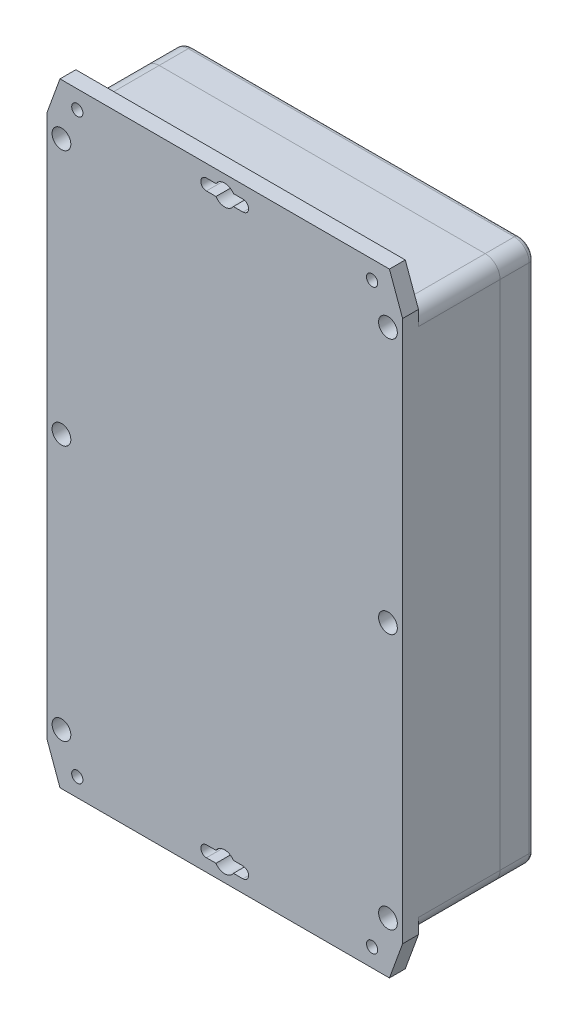
SolidWorks part; units mm, degrees
ref_plane "Front Plane" through (0, 0, 0) normal (0, 0, 1) x (1, 0, 0)
ref_plane "Top Plane" through (0, 0, 0) normal (0, 1, 0) x (1, 0, 0)
ref_plane "Right Plane" through (0, 0, 0) normal (1, 0, 0) x (0, 0, -1)
sketch "Sketch1" plane through (0, 0, 0) normal (0, 0, 1) x (1, 0, 0)
  line L0 (-73.025, -125.9967) -> (73.025, 125.9967) construction
  line L1 (-73.025, 125.9967) -> (73.025, 125.9967)
  line L2 (-73.025, 125.9967) -> (-73.025, -125.9967)
  line L3 (-73.025, -125.9967) -> (73.025, -125.9967)
  line L4 (73.025, 125.9967) -> (73.025, -125.9967)
  line L5 (0, 118.5037) -> (0, -118.5037) construction
  line L6 (-7.5057, 118.5037) -> (7.5057, 118.5037) construction
  line L7 (-7.5057, 120.8024) -> (-3.58, 120.8024)
  line L8 (-7.5057, 116.205) -> (-3.58, 116.205)
  line L9 (3.58, 120.8024) -> (7.5057, 120.8024)
  line L10 (3.58, 116.205) -> (7.5057, 116.205)
  line L11 (-73.025, 0) -> (73.025, 0) construction
  line L12 (-7.5057, -116.205) -> (-3.58, -116.205)
  line L13 (3.58, -116.205) -> (7.5057, -116.205)
  line L14 (3.58, -120.8024) -> (7.5057, -120.8024)
  line L15 (-7.5057, -120.8024) -> (-3.58, -120.8024)
  line L16 (-67.0052, 105.0036) -> (67.0052, -105.0036) construction
  line L17 (0, -114.2492) -> (0, -122.7582) construction
  line L18 (0, 114.2492) -> (0, 122.7582) construction
  line L19 (-60.5028, 118.5037) -> (60.5028, 118.5037) construction
  line L20 (-60.5028, -118.5037) -> (60.5028, -118.5037) construction
  line L21 (0, -118.5037) -> (0, 118.5037) construction
  arc A0 (3.58, 120.8024) -> (-3.58, 120.8024) centre (0, 118.5037) ccw
  arc A1 (-7.5057, 120.8024) -> (-7.5057, 116.205) centre (-7.5057, 118.5037) ccw
  arc A2 (7.5057, 116.205) -> (7.5057, 120.8024) centre (7.5057, 118.5037) ccw
  arc A3 (-3.58, 116.205) -> (3.58, 116.205) centre (0, 118.5037) ccw
  arc A4 (-3.58, -116.205) -> (3.58, -116.205) centre (0, -118.5037) cw
  arc A5 (7.5057, -116.205) -> (7.5057, -120.8024) centre (7.5057, -118.5037) cw
  arc A6 (3.58, -120.8024) -> (-3.58, -120.8024) centre (0, -118.5037) cw
  arc A7 (-7.5057, -120.8024) -> (-7.5057, -116.205) centre (-7.5057, -118.5037) cw
  circle A8 centre (67.0052, 105.0036) radius 2.2225
  circle A9 centre (67.0052, 105.0036) radius 3.8481
  circle A10 centre (67.0052, -105.0036) radius 3.8481
  circle A11 centre (67.0052, -105.0036) radius 2.2225
  circle A12 centre (-67.0052, -105.0036) radius 3.8481
  circle A13 centre (-67.0052, -105.0036) radius 2.2225
  circle A14 centre (-67.0052, 105.0036) radius 3.8481
  circle A15 centre (-67.0052, 105.0036) radius 2.2225
  circle A16 centre (60.5028, 118.5037) radius 2.2987
  circle A17 centre (-60.5028, 118.5037) radius 2.2987
  circle A18 centre (-60.5028, -118.5037) radius 2.2987
  circle A19 centre (60.5028, -118.5037) radius 2.2987
  circle A20 centre (-67.0052, 0) radius 3.8481
  circle A21 centre (-67.0052, 0) radius 2.2225
  circle A22 centre (67.0052, 0) radius 3.8481
  circle A23 centre (67.0052, 0) radius 2.2225
  dimension "D4" = 8.509
  dimension "D5" = 4.5974
  dimension "D7" = 7.6962
  dimension "D8" = 4.445
  dimension "Width" = 146.05
  dimension "Total Height" = 251.9934
  dimension "Hole Location" = 237.0074
  dimension "D6" = 15.0114
  dimension "A" = 210.0072
  dimension "B" = 134.0104
  dimension "flange holes" = 121.0056
sketch "Sketch18" plane through (0, 0, 0) normal (1, 0, 0) x (0, 0, -1)
  line L0 (0, 0) -> (53.975, 0) construction
  point P3 (40.005, 0)
  dimension "Depth" = 53.975
  dimension "Base Depth" = 40.005
sketch "Sketch2" plane through (0, 0, 0) normal (0, 0, 1) x (1, 0, 0)
  line L4 (73.025, 125.9967) -> (-73.025, 125.9967)
  line L5 (73.025, -125.9967) -> (73.025, 125.9967)
  line L6 (-73.025, -125.9967) -> (73.025, -125.9967)
  line L7 (-73.025, 125.9967) -> (-73.025, -125.9967)
  line L8 (73.025, 125.9967) -> (-73.025, 125.9967)
  line L9 (73.025, -125.9967) -> (73.025, 125.9967)
  line L10 (-73.025, -125.9967) -> (73.025, -125.9967)
  line L11 (-73.025, 125.9967) -> (-73.025, -125.9967)
  line L12 (-7.5057, -120.8024) -> (-3.58, -120.8024)
  line L13 (3.58, -120.8024) -> (7.5057, -120.8024)
  line L14 (7.5057, -116.205) -> (3.58, -116.205)
  line L15 (-3.58, -116.205) -> (-7.5057, -116.205)
  line L16 (-7.5057, -120.8024) -> (-3.58, -120.8024)
  line L17 (3.58, -120.8024) -> (7.5057, -120.8024)
  line L18 (7.5057, -116.205) -> (3.58, -116.205)
  line L19 (-3.58, -116.205) -> (-7.5057, -116.205)
  line L20 (-3.58, 120.8024) -> (-7.5057, 120.8024)
  line L21 (-7.5057, 116.205) -> (-3.58, 116.205)
  line L22 (3.58, 116.205) -> (7.5057, 116.205)
  line L23 (7.5057, 120.8024) -> (3.58, 120.8024)
  line L24 (-3.58, 120.8024) -> (-7.5057, 120.8024)
  line L25 (-7.5057, 116.205) -> (-3.58, 116.205)
  line L26 (3.58, 116.205) -> (7.5057, 116.205)
  line L27 (7.5057, 120.8024) -> (3.58, 120.8024)
  circle A0 centre (60.5028, 118.5037) radius 2.2987 construction
  circle A1 centre (-60.5028, 118.5037) radius 2.2987 construction
  circle A2 centre (-60.5028, -118.5037) radius 2.2987 construction
  circle A3 centre (60.5028, -118.5037) radius 2.2987 construction
  circle A4 centre (60.5028, 118.5037) radius 2.2987
  circle A5 centre (-60.5028, 118.5037) radius 2.2987
  circle A6 centre (-60.5028, -118.5037) radius 2.2987
  circle A7 centre (60.5028, -118.5037) radius 2.2987
  arc A8 (-7.5057, -116.205) -> (-7.5057, -120.8024) centre (-7.5057, -118.5037) ccw
  arc A9 (-3.58, -120.8024) -> (3.58, -120.8024) centre (0, -118.5037) ccw
  arc A10 (7.5057, -120.8024) -> (7.5057, -116.205) centre (7.5057, -118.5037) ccw
  arc A11 (3.58, -116.205) -> (-3.58, -116.205) centre (0, -118.5037) ccw
  arc A12 (-7.5057, -116.205) -> (-7.5057, -120.8024) centre (-7.5057, -118.5037) ccw
  arc A13 (-3.58, -120.8024) -> (3.58, -120.8024) centre (0, -118.5037) ccw
  arc A14 (7.5057, -120.8024) -> (7.5057, -116.205) centre (7.5057, -118.5037) ccw
  arc A15 (3.58, -116.205) -> (-3.58, -116.205) centre (0, -118.5037) ccw
  arc A16 (-7.5057, 120.8024) -> (-7.5057, 116.205) centre (-7.5057, 118.5037) ccw
  arc A17 (-3.58, 116.205) -> (3.58, 116.205) centre (0, 118.5037) ccw
  arc A18 (7.5057, 116.205) -> (7.5057, 120.8024) centre (7.5057, 118.5037) ccw
  arc A19 (3.58, 120.8024) -> (-3.58, 120.8024) centre (0, 118.5037) ccw
  arc A20 (-7.5057, 120.8024) -> (-7.5057, 116.205) centre (-7.5057, 118.5037) ccw
  arc A21 (-3.58, 116.205) -> (3.58, 116.205) centre (0, 118.5037) ccw
  arc A22 (7.5057, 116.205) -> (7.5057, 120.8024) centre (7.5057, 118.5037) ccw
  arc A23 (3.58, 120.8024) -> (-3.58, 120.8024) centre (0, 118.5037) ccw
  dimension "D1" = 0
  dimension "D4" = 0
  dimension "D5" = 0
extrude "Boss-Extrude1" add sketch "Sketch2" against normal blind 6.5024
sketch "Sketch3" plane through (0, 0, -6.5024) normal (0, 0, -1) x (-1, 0, 0)
  line L0 (73.025, 111.125) -> (67.6121, 125.9967)
  line L1 (-73.025, 111.125) -> (-67.6121, 125.9967)
  line L2 (73.025, -111.125) -> (67.6121, -125.9967)
  line L3 (-73.025, -111.125) -> (-67.6121, -125.9967)
  line L4 (73.025, -125.9967) -> (73.025, 125.9967)
  line L5 (73.025, 125.9967) -> (-73.025, 125.9967)
  line L6 (-73.025, 125.9967) -> (-73.025, -125.9967)
  line L7 (-73.025, -125.9967) -> (73.025, -125.9967)
  line L8 (73.025, -125.9967) -> (73.025, -111.125)
  line L9 (73.025, 125.9967) -> (67.6121, 125.9967)
  line L10 (-73.025, 125.9967) -> (-73.025, 111.125)
  line L11 (-73.025, -125.9967) -> (-67.6121, -125.9967)
  line L12 (-67.6121, 125.9967) -> (-73.025, 125.9967)
  line L13 (73.025, -125.9967) -> (-73.025, -125.9967) construction
  line L14 (67.6121, -125.9967) -> (73.025, -125.9967)
  line L15 (-73.025, -111.125) -> (-73.025, -125.9967)
  line L16 (73.025, 111.125) -> (73.025, 125.9967)
  line L19 (73.025, 111.125) -> (73.025, -111.125) construction
  dimension "D2" = 20
  dimension "D3" = 20
  dimension "Height" = 222.25
  dimension "D1" = 0
extrude "Cut-Extrude1" cut sketch "Sketch3" against normal through all
sketch "Sketch4" plane through (0, 0, -6.5024) normal (0, 0, 1) x (1, 0, 0)
  line L0 (-68.453, 106.553) -> (68.453, 106.553) construction
  line L1 (-73.025, 111.125) -> (73.025, 111.125)
  line L2 (-73.025, 111.125) -> (-73.025, -111.125)
  line L3 (-73.025, -111.125) -> (73.025, -111.125)
  line L4 (73.025, 111.125) -> (73.025, -111.125)
  line L5 (68.453, 106.553) -> (68.453, -106.553) construction
  line L6 (-68.453, -106.553) -> (68.453, -106.553) construction
  line L7 (-68.453, 106.553) -> (-68.453, -106.553) construction
  line L8 (-70.485, 108.585) -> (70.485, 108.585) construction
  line L9 (73.025, 125.9967) -> (73.025, -125.9967) construction
  line L10 (70.485, 108.585) -> (70.485, -108.585) construction
  line L11 (-70.485, -108.585) -> (70.485, -108.585) construction
  line L12 (-70.485, 108.585) -> (-70.485, -108.585) construction
  circle A0 centre (67.0052, 105.0036) radius 6.1214 construction
  circle A1 centre (-67.0052, 105.0036) radius 6.1214 construction
  circle A2 centre (-67.0052, -105.0036) radius 6.1214 construction
  circle A3 centre (67.0052, -105.0036) radius 6.1214 construction
  dimension "D3" = 12.2428
  dimension "D1" = 4.572
  dimension "D2" = 2.032
extrude "Boss-Extrude2" add sketch "Sketch4" against normal up to vertex (33.5026 mm away) up to point (0, 0, -40.005)
sketch "Sketch5" plane through (0, 0, 0) normal (0, 0, -1) x (-1, 0, 0)
  circle A0 centre (67.0052, 105.0036) radius 3.8481 construction
  circle A1 centre (-67.0052, 105.0036) radius 3.8481 construction
  circle A2 centre (-67.0052, -105.0036) radius 3.8481 construction
  circle A3 centre (67.0052, -105.0036) radius 3.8481 construction
  circle A4 centre (67.0052, 105.0036) radius 3.8481
  circle A5 centre (-67.0052, 105.0036) radius 3.8481
  circle A6 centre (-67.0052, -105.0036) radius 3.8481
  circle A7 centre (67.0052, -105.0036) radius 3.8481
  circle A8 centre (-67.0052, 0) radius 3.8481 construction
  circle A9 centre (67.0052, 0) radius 3.8481 construction
  circle A10 centre (-67.0052, 0) radius 3.8481
  circle A11 centre (67.0052, 0) radius 3.8481
extrude "Cut-Extrude2" cut sketch "Sketch5" along normal blind 24.003
sketch "Sketch6" plane through (0, 0, -24.003) normal (0, 0, 1) x (1, 0, 0)
  circle A0 centre (-67.0052, 105.0036) radius 2.2225 construction
  circle A1 centre (67.0052, 105.0036) radius 2.2225 construction
  circle A2 centre (67.0052, -105.0036) radius 2.2225 construction
  circle A3 centre (-67.0052, -105.0036) radius 2.2225 construction
  circle A4 centre (-67.0052, 105.0036) radius 2.2225
  circle A5 centre (67.0052, 105.0036) radius 2.2225
  circle A6 centre (67.0052, -105.0036) radius 2.2225
  circle A7 centre (-67.0052, -105.0036) radius 2.2225
  circle A8 centre (67.0052, 0) radius 2.2225 construction
  circle A9 centre (-67.0052, 0) radius 2.2225 construction
  circle A10 centre (67.0052, 0) radius 2.2225
  circle A11 centre (-67.0052, 0) radius 2.2225
extrude "Cut-Extrude3" cut sketch "Sketch6" against normal through all
sketch "Sketch7" plane through (0, 0, -40.005) normal (0, 0, -1) x (-1, 0, 0)
  line L0 (70.485, 108.585) -> (-70.485, 108.585) construction
  line L1 (70.485, 108.585) -> (70.485, -108.585) construction
  line L2 (-70.485, 108.585) -> (-70.485, -108.585) construction
  line L4 (46.6471, 108.585) -> (-46.6471, 108.585)
  line L5 (70.485, 95.4024) -> (70.485, -95.4024)
  line L6 (-70.485, 95.4024) -> (-70.485, -95.4024)
  line L8 (-51.4985, 103.7336) -> (-51.4985, 98.8822) construction
  line L9 (-67.0052, 98.8822) -> (-56.3499, 98.8822)
  line L12 (46.6471, -108.585) -> (-46.6471, -108.585)
  line L13 (0, 0) -> (0, 108.585) construction
  line L14 (67.0052, 98.8822) -> (56.3499, 98.8822)
  line L15 (0, 0) -> (-70.485, 0) construction
  line L16 (67.0052, -98.8822) -> (56.3499, -98.8822)
  line L17 (-67.0052, -98.8822) -> (-56.3499, -98.8822)
  circle A0 centre (-67.0052, 105.0036) radius 6.1214 construction
  arc A1 (51.4985, -103.7336) -> (46.6471, -108.585) centre (46.6471, -103.7336) cw
  circle A2 centre (67.0052, -105.0036) radius 6.1214 construction
  circle A4 centre (-67.0052, 105.0036) radius 6.1214 construction
  circle A6 centre (67.0052, -105.0036) radius 6.1214 construction
  arc A14 (-67.0052, 98.8822) -> (-70.485, 95.4024) centre (-67.0052, 95.4024) ccw
  arc A22 (-51.4985, 103.7336) -> (-46.6471, 108.585) centre (-46.6471, 103.7336) cw
  arc A24 (67.0052, 98.8822) -> (70.485, 95.4024) centre (67.0052, 95.4024) cw
  arc A25 (-56.3499, 98.8822) -> (-51.4985, 103.7336) centre (-56.3499, 103.7336) ccw
  circle A26 centre (-67.0052, 105.0036) radius 2.2225 construction
  circle A27 centre (67.0052, 105.0036) radius 6.1214 construction
  arc A28 (56.3499, 98.8822) -> (51.4985, 103.7336) centre (56.3499, 103.7336) cw
  arc A29 (51.4985, 103.7336) -> (46.6471, 108.585) centre (46.6471, 103.7336) ccw
  arc A30 (56.3499, -98.8822) -> (51.4985, -103.7336) centre (56.3499, -103.7336) ccw
  arc A31 (-51.4985, -103.7336) -> (-46.6471, -108.585) centre (-46.6471, -103.7336) ccw
  arc A32 (-56.3499, -98.8822) -> (-51.4985, -103.7336) centre (-56.3499, -103.7336) cw
  arc A33 (67.0052, -98.8822) -> (70.485, -95.4024) centre (67.0052, -95.4024) ccw
  arc A34 (-67.0052, -98.8822) -> (-70.485, -95.4024) centre (-67.0052, -95.4024) cw
  dimension "D1" = 102.997
sketch "Sketch8" plane through (0, 0, -40.005) normal (0, 0, -1) x (-1, 0, 0)
  line L0 (-67.0052, -6.1214) -> (-70.485, -6.1214)
  line L1 (-67.0052, 6.1214) -> (-70.485, 6.1214)
  line L2 (67.0052, 6.1214) -> (70.485, 6.1214)
  line L3 (67.0052, -6.1214) -> (70.485, -6.1214)
  line L4 (-70.485, -6.1214) -> (-70.485, -95.4024)
  line L5 (70.485, 6.1214) -> (70.485, 95.4024)
  line L8 (46.6471, 108.585) -> (-46.6471, 108.585)
  line L9 (-56.3499, 98.8822) -> (-67.0052, 98.8822)
  line L10 (-70.485, 95.4024) -> (-70.485, -95.4024)
  line L11 (-67.0052, -98.8822) -> (-56.3499, -98.8822)
  line L12 (-46.6471, -108.585) -> (46.6471, -108.585)
  line L13 (56.3499, -98.8822) -> (67.0052, -98.8822)
  line L14 (70.485, -95.4024) -> (70.485, 95.4024)
  line L15 (67.0052, 98.8822) -> (56.3499, 98.8822)
  line L16 (46.6471, 108.585) -> (-46.6471, 108.585)
  line L17 (-56.3499, 98.8822) -> (-67.0052, 98.8822)
  line L18 (-70.485, 95.4024) -> (-70.485, 6.1214)
  line L19 (-67.0052, -98.8822) -> (-56.3499, -98.8822)
  line L20 (-46.6471, -108.585) -> (46.6471, -108.585)
  line L21 (56.3499, -98.8822) -> (67.0052, -98.8822)
  line L22 (70.485, -95.4024) -> (70.485, -6.1214)
  line L23 (67.0052, 98.8822) -> (56.3499, 98.8822)
  arc A0 (-67.0052, -6.1214) -> (-67.0052, 6.1214) centre (-67.0052, 0) ccw
  arc A1 (67.0052, 6.1214) -> (67.0052, -6.1214) centre (67.0052, 0) ccw
  circle A4 centre (-67.0052, 105.0036) radius 6.1214 construction
  arc A13 (-46.6471, 108.585) -> (-51.4985, 103.7336) centre (-46.6471, 103.7336) ccw
  arc A14 (-56.3499, 98.8822) -> (-51.4985, 103.7336) centre (-56.3499, 103.7336) ccw
  arc A15 (-67.0052, 98.8822) -> (-70.485, 95.4024) centre (-67.0052, 95.4024) ccw
  arc A16 (-70.485, -95.4024) -> (-67.0052, -98.8822) centre (-67.0052, -95.4024) ccw
  arc A17 (-51.4985, -103.7336) -> (-56.3499, -98.8822) centre (-56.3499, -103.7336) ccw
  arc A18 (-51.4985, -103.7336) -> (-46.6471, -108.585) centre (-46.6471, -103.7336) ccw
  arc A19 (46.6471, -108.585) -> (51.4985, -103.7336) centre (46.6471, -103.7336) ccw
  arc A20 (56.3499, -98.8822) -> (51.4985, -103.7336) centre (56.3499, -103.7336) ccw
  arc A21 (67.0052, -98.8822) -> (70.485, -95.4024) centre (67.0052, -95.4024) ccw
  arc A22 (70.485, 95.4024) -> (67.0052, 98.8822) centre (67.0052, 95.4024) ccw
  arc A23 (51.4985, 103.7336) -> (56.3499, 98.8822) centre (56.3499, 103.7336) ccw
  arc A24 (51.4985, 103.7336) -> (46.6471, 108.585) centre (46.6471, 103.7336) ccw
  arc A25 (-46.6471, 108.585) -> (-51.4985, 103.7336) centre (-46.6471, 103.7336) ccw
  arc A26 (-56.3499, 98.8822) -> (-51.4985, 103.7336) centre (-56.3499, 103.7336) ccw
  arc A27 (-67.0052, 98.8822) -> (-70.485, 95.4024) centre (-67.0052, 95.4024) ccw
  arc A28 (-70.485, -95.4024) -> (-67.0052, -98.8822) centre (-67.0052, -95.4024) ccw
  arc A29 (-51.4985, -103.7336) -> (-56.3499, -98.8822) centre (-56.3499, -103.7336) ccw
  arc A30 (-51.4985, -103.7336) -> (-46.6471, -108.585) centre (-46.6471, -103.7336) ccw
  arc A31 (46.6471, -108.585) -> (51.4985, -103.7336) centre (46.6471, -103.7336) ccw
  arc A32 (56.3499, -98.8822) -> (51.4985, -103.7336) centre (56.3499, -103.7336) ccw
  arc A33 (67.0052, -98.8822) -> (70.485, -95.4024) centre (67.0052, -95.4024) ccw
  arc A34 (70.485, 95.4024) -> (67.0052, 98.8822) centre (67.0052, 95.4024) ccw
  arc A35 (51.4985, 103.7336) -> (56.3499, 98.8822) centre (56.3499, 103.7336) ccw
  arc A36 (51.4985, 103.7336) -> (46.6471, 108.585) centre (46.6471, 103.7336) ccw
  point P2 (-19.1135, 50.2285)
  point P3 (-19.1135, 56.896)
  point P4 (22.9997, -25.9969)
  point P8 (-25.781, 50.2285)
  point P11 (-26.035, 21.1097)
  point P13 (26.035, -21.1097)
  point P14 (-27.8765, 48.133)
  point P18 (-41.91, -42.9387)
  point P19 (-39.0017, 48.133)
  point P29 (-19.1135, 50.2285)
  point P30 (-19.1135, 56.896)
  point P33 (41.91, 42.9387)
  point P34 (-25.781, 50.2285)
  point P37 (-27.8765, 48.133)
  point P39 (-39.0017, 48.133)
  point P52 (31.0388, -25.9969)
  point P57 (-24.003, -17.2085)
  point P58 (-24.003, 18.2767)
  point P59 (-22.9997, 25.9969)
  point P60 (-15.2146, 25.9969)
  point P61 (-19.2786, 25.9969)
  point P62 (-19.2786, 16.0147)
  point P63 (-22.9997, 25.9969)
  point P64 (-19.2786, 25.9969)
  point P65 (-14.9606, 25.9969)
  point P67 (-22.9997, 12.2936)
  point P68 (-19.2786, 15.8369)
  point P69 (-22.9997, 7.2263)
  point P70 (-28.067, 7.2263)
  point P75 (15.2146, -25.9969)
  point P97 (24.003, 17.2085)
  point P98 (24.003, -18.2767)
  point P99 (22.9997, -25.9969)
  point P100 (22.9997, -7.2263)
  point P101 (22.9997, -12.2936)
  point P102 (28.067, -7.2263)
  point P104 (19.2786, -16.0147)
  point P105 (19.2786, -25.9969)
  dimension "D1" = 0
extrude "Cut-Extrude4" cut sketch "Sketch8" against normal offset from surface (37.0078 mm away) 2.9972 up to face at (63.1571, 0, 0)
sketch "Sketch9" plane through (0, 0, 0) normal (0, 0, -1) x (-1, 0, 0)
  line L1 (-19.4945, 82.9945) -> (19.4945, 82.9945) construction
  line L2 (0, 82.9945) -> (0, 0) construction
  line L3 (0, 82.9945) -> (0, 90.7542) construction
  line L4 (-57.7469, 90.7542) -> (57.7469, 90.7542) construction
  line L5 (0, 0) -> (-36.6733, 0) construction
  line L6 (-57.7469, -90.7542) -> (57.7469, -90.7542) construction
  line L7 (-19.4945, -82.9945) -> (19.4945, -82.9945) construction
  line L8 (0, -82.9945) -> (0, -90.7542) construction
  line L9 (0, -82.9945) -> (0, 0) construction
  circle A0 centre (-57.7469, 90.7542) radius 3.0099
  circle A1 centre (-57.7469, 90.7542) radius 1.2446
  circle A2 centre (57.7469, 90.7542) radius 3.0099
  circle A3 centre (57.7469, 90.7542) radius 1.2446
  circle A4 centre (-19.4945, 82.9945) radius 3.0099
  circle A5 centre (-19.4945, 82.9945) radius 1.2446
  circle A6 centre (19.4945, 82.9945) radius 3.0099
  circle A7 centre (19.4945, 82.9945) radius 1.2446
  circle A8 centre (57.7469, -90.7542) radius 1.2446
  circle A9 centre (57.7469, -90.7542) radius 3.0099
  circle A10 centre (19.4945, -82.9945) radius 1.2446
  circle A11 centre (-19.4945, -82.9945) radius 1.2446
  circle A12 centre (-19.4945, -82.9945) radius 3.0099
  circle A13 centre (-57.7469, -90.7542) radius 1.2446
  circle A14 centre (-57.7469, -90.7542) radius 3.0099
  circle A15 centre (19.4945, -82.9945) radius 3.0099
  dimension "D2" = 2.4892
  dimension "D3" = 6.0198
  dimension "D1" = 2.4892
  dimension "D4" = 6.0198
  dimension "D5" = 2.4892
  dimension "D6" = 6.0198
  dimension "D9" = 165.989
  dimension "D10" = 181.5084
  dimension "D7" = 38.989
  dimension "D8" = 115.4938
extrude "Boss-Extrude3" add sketch "Sketch9" along normal blind 7.493
fillet "Fillet2" radius 6.1214 4 edges at (73.025, 111.125, -23.2537) (73.025, -111.125, -23.2537) (-73.025, -111.125, -23.2537) (-73.025, 111.125, -23.2537) tangent propagation no
sketch "Sketch11" plane through (0, 0, -40.005) normal (0, 0, -1) x (-1, 0, 0)
  line L4 (-73.025, 105.0036) -> (-73.025, -105.0036)
  line L5 (66.9036, 111.125) -> (-66.9036, 111.125)
  line L6 (73.025, -105.0036) -> (73.025, 105.0036)
  line L7 (-66.9036, -111.125) -> (66.9036, -111.125)
  line L8 (-73.025, 105.0036) -> (-73.025, -105.0036)
  line L9 (66.9036, 111.125) -> (-66.9036, 111.125)
  line L10 (73.025, -105.0036) -> (73.025, 105.0036)
  line L11 (-66.9036, -111.125) -> (66.9036, -111.125)
  arc A4 (-66.9036, 111.125) -> (-73.025, 105.0036) centre (-66.9036, 105.0036) ccw
  arc A5 (73.025, 105.0036) -> (66.9036, 111.125) centre (66.9036, 105.0036) ccw
  arc A6 (66.9036, -111.125) -> (73.025, -105.0036) centre (66.9036, -105.0036) ccw
  arc A7 (-73.025, -105.0036) -> (-66.9036, -111.125) centre (-66.9036, -105.0036) ccw
  arc A8 (-66.9036, 111.125) -> (-73.025, 105.0036) centre (-66.9036, 105.0036) ccw
  arc A9 (73.025, 105.0036) -> (66.9036, 111.125) centre (66.9036, 105.0036) ccw
  arc A10 (66.9036, -111.125) -> (73.025, -105.0036) centre (66.9036, -105.0036) ccw
  arc A11 (-73.025, -105.0036) -> (-66.9036, -111.125) centre (-66.9036, -105.0036) ccw
  dimension "D1" = 0
extrude "Boss-Extrude4" add sketch "Sketch11" along normal up to vertex (13.97 mm away) separate body up to point (0, 0, -53.975)
sketch "Sketch12" plane through (0, 0, -53.975) normal (0, 0, -1) x (-1, 0, 0)
  circle A0 centre (-67.0052, 105.0036) radius 3.8481 construction
  circle A1 centre (67.0052, 105.0036) radius 3.8481 construction
  circle A2 centre (67.0052, -105.0036) radius 3.8481 construction
  circle A3 centre (-67.0052, -105.0036) radius 3.8481 construction
  circle A4 centre (-67.0052, 105.0036) radius 3.8481
  circle A5 centre (67.0052, 105.0036) radius 3.8481
  circle A6 centre (67.0052, -105.0036) radius 3.8481
  circle A7 centre (-67.0052, -105.0036) radius 3.8481
  circle A8 centre (-67.0052, 0) radius 3.8481 construction
  circle A9 centre (67.0052, 0) radius 3.8481 construction
  circle A10 centre (-67.0052, 0) radius 3.8481
  circle A11 centre (67.0052, 0) radius 3.8481
extrude "Cut-Extrude5" cut sketch "Sketch12" against normal blind 3.2004
shell "Shell1" thickness 2.9972 removed face at (0, 0, -40.005)
fillet "Fillet3" radius 2.032 8 edges at (-71.2321, 109.3321, -53.975) (0, 111.125, -53.975) (71.2321, 109.3321, -53.975) (73.025, 0, -53.975) (71.2321, -109.3321, -53.975) (0, -111.125, -53.975) (-71.2321, -109.3321, -53.975) (-73.025, 0, -53.975)
sketch "Sketch13" plane through (0, 0, -50.7746) normal (0, 0, -1) x (-1, 0, 0)
  circle A0 centre (-67.0052, 0) radius 3.5941
  circle A1 centre (67.0052, 105.0036) radius 3.5941
  circle A2 centre (-67.0052, 105.0036) radius 3.5941
  circle A3 centre (-67.0052, 105.0036) radius 3.5941
  circle A4 centre (67.0052, -105.0036) radius 3.5941
  circle A5 centre (-67.0052, -105.0036) radius 3.5941
  circle A6 centre (67.0052, 0) radius 3.5941
  dimension "D1" = 0.254
extrude "Boss-Extrude6" add sketch "Sketch13" along normal blind 2.286 separate body
sketch "Sketch14" plane through (0, 0, -50.7746) normal (0, 0, 1) x (1, 0, 0)
  circle A0 centre (-67.0052, 105.0036) radius 2.2225 construction
  circle A1 centre (-67.0052, 105.0036) radius 2.2225
  circle A2 centre (-67.0052, -105.0036) radius 2.2225 construction
  circle A3 centre (67.0052, -105.0036) radius 2.2225 construction
  circle A4 centre (-67.0052, -105.0036) radius 2.2225
  circle A5 centre (67.0052, -105.0036) radius 2.2225
  circle A6 centre (67.0052, 105.0036) radius 2.2225 construction
  circle A7 centre (67.0052, 105.0036) radius 2.2225
  circle A8 centre (67.0052, 0) radius 2.2225 construction
  circle A9 centre (67.0052, 0) radius 2.2225
  circle A10 centre (-67.0052, 0) radius 2.2225 construction
  circle A11 centre (-67.0052, 0) radius 2.2225
extrude "Boss-Extrude7" add sketch "Sketch14" along normal offset from surface (29.8196 mm away) 3.048 up to face at (-64.7827, 105.0036, -24.003) offset beyond the face yes
fillet "Fillet4" radius 1.27 6 edges at (-70.5993, -105.0036, -53.0606) (63.4111, -105.0036, -53.0606) (-70.5993, 105.0036, -53.0606) (63.4111, 105.0036, -53.0606) (-70.5993, 0, -53.0606) (63.4111, 0, -53.0606)
sketch "Sketch15" plane through (0, 0, -53.0606) normal (0, 0, -1) x (-1, 0, 0)
  line L0 (-67.0052, 111.125) -> (-67.0052, -111.125)
  line L1 (-66.9036, -111.125) -> (66.9036, -111.125) construction
  line L2 (66.9036, 111.125) -> (-66.9036, 111.125) construction
  circle A0 centre (-67.0052, 105.0036) radius 2.3241 construction
  circle A1 centre (-67.0052, 105.0036) radius 2.3241 construction
extrude "Cut-Extrude-Thin1" cut sketch "Sketch15" against normal blind 1.524 thin thin type mid plane wall 1.524
mirror "Mirror1" about plane through (0, 0, 0) normal (1, 0, 0) of "Cut-Extrude-Thin1"
sketch "Sketch16" plane through (0, 0, -40.005) normal (0, 0, -1) x (-1, 0, 0)
  line L8 (46.6471, 108.585) -> (-46.6471, 108.585)
  line L9 (-56.3499, 98.8822) -> (-67.0052, 98.8822)
  line L10 (-70.485, 95.4024) -> (-70.485, -95.4024)
  line L11 (-67.0052, -98.8822) -> (-56.3499, -98.8822)
  line L12 (-46.6471, -108.585) -> (46.6471, -108.585)
  line L13 (56.3499, -98.8822) -> (67.0052, -98.8822)
  line L14 (70.485, -95.4024) -> (70.485, 95.4024)
  line L15 (67.0052, 98.8822) -> (56.3499, 98.8822)
  line L16 (46.6471, 108.585) -> (-46.6471, 108.585)
  line L17 (-56.3499, 98.8822) -> (-67.0052, 98.8822)
  line L18 (-70.485, 95.4024) -> (-70.485, -95.4024)
  line L19 (-67.0052, -98.8822) -> (-56.3499, -98.8822)
  line L20 (-46.6471, -108.585) -> (46.6471, -108.585)
  line L21 (56.3499, -98.8822) -> (67.0052, -98.8822)
  line L22 (70.485, -95.4024) -> (70.485, 95.4024)
  line L23 (67.0052, 98.8822) -> (56.3499, 98.8822)
  arc A12 (-46.6471, 108.585) -> (-51.4985, 103.7336) centre (-46.6471, 103.7336) ccw
  arc A13 (-56.3499, 98.8822) -> (-51.4985, 103.7336) centre (-56.3499, 103.7336) ccw
  arc A14 (-67.0052, 98.8822) -> (-70.485, 95.4024) centre (-67.0052, 95.4024) ccw
  arc A15 (-70.485, -95.4024) -> (-67.0052, -98.8822) centre (-67.0052, -95.4024) ccw
  arc A16 (-51.4985, -103.7336) -> (-56.3499, -98.8822) centre (-56.3499, -103.7336) ccw
  arc A17 (-51.4985, -103.7336) -> (-46.6471, -108.585) centre (-46.6471, -103.7336) ccw
  arc A18 (46.6471, -108.585) -> (51.4985, -103.7336) centre (46.6471, -103.7336) ccw
  arc A19 (56.3499, -98.8822) -> (51.4985, -103.7336) centre (56.3499, -103.7336) ccw
  arc A20 (67.0052, -98.8822) -> (70.485, -95.4024) centre (67.0052, -95.4024) ccw
  arc A21 (70.485, 95.4024) -> (67.0052, 98.8822) centre (67.0052, 95.4024) ccw
  arc A22 (51.4985, 103.7336) -> (56.3499, 98.8822) centre (56.3499, 103.7336) ccw
  arc A23 (51.4985, 103.7336) -> (46.6471, 108.585) centre (46.6471, 103.7336) ccw
  arc A24 (-46.6471, 108.585) -> (-51.4985, 103.7336) centre (-46.6471, 103.7336) ccw
  arc A25 (-56.3499, 98.8822) -> (-51.4985, 103.7336) centre (-56.3499, 103.7336) ccw
  arc A26 (-67.0052, 98.8822) -> (-70.485, 95.4024) centre (-67.0052, 95.4024) ccw
  arc A27 (-70.485, -95.4024) -> (-67.0052, -98.8822) centre (-67.0052, -95.4024) ccw
  arc A28 (-51.4985, -103.7336) -> (-56.3499, -98.8822) centre (-56.3499, -103.7336) ccw
  arc A29 (-51.4985, -103.7336) -> (-46.6471, -108.585) centre (-46.6471, -103.7336) ccw
  arc A30 (46.6471, -108.585) -> (51.4985, -103.7336) centre (46.6471, -103.7336) ccw
  arc A31 (56.3499, -98.8822) -> (51.4985, -103.7336) centre (56.3499, -103.7336) ccw
  arc A32 (67.0052, -98.8822) -> (70.485, -95.4024) centre (67.0052, -95.4024) ccw
  arc A33 (70.485, 95.4024) -> (67.0052, 98.8822) centre (67.0052, 95.4024) ccw
  arc A34 (51.4985, 103.7336) -> (56.3499, 98.8822) centre (56.3499, 103.7336) ccw
  arc A35 (51.4985, 103.7336) -> (46.6471, 108.585) centre (46.6471, 103.7336) ccw
  dimension "D1" = 0
ref_plane "Plane1" through (0, 95.4024, 0) normal (0, 1, 0) x (-1, 0, 0)
sketch "Sketch17" plane through (0, 95.4024, 0) normal (0, 1, 0) x (-1, 0, 0)
  line L0 (-71.755, -40.005) -> (-70.485, -40.005)
  arc A0 (-71.755, -40.005) -> (-70.485, -40.005) centre (-71.12, -40.005) ccw
  dimension "D1" = 1.27
sweep "Sweep1" add profiles "Sketch17" path "Sketch16"
equation "\"D1@Fillet2\" = \"D3@Sketch4\"/2"
equation "\"D1@Cut-Extrude2\" = \"Base Depth@Sketch18\"*.6"
